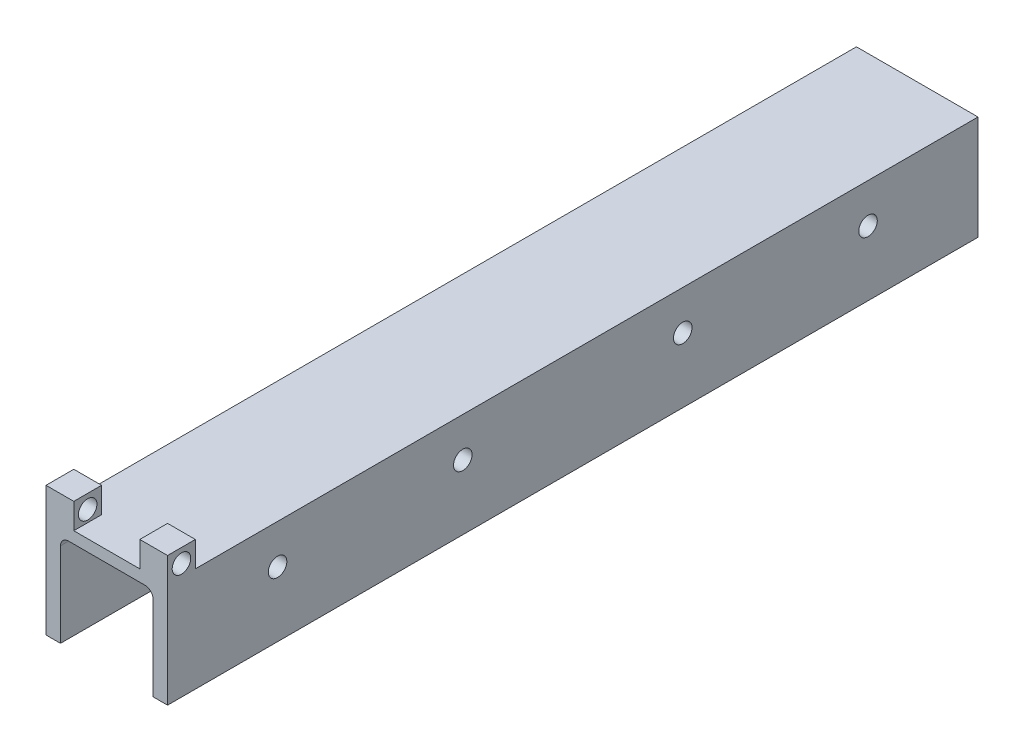
SolidWorks part; units mm, degrees
ref_plane "Front Plane" through (0, 0, 0) normal (0, 0, 1) x (1, 0, 0)
ref_plane "Top Plane" through (0, 0, 0) normal (0, 1, 0) x (1, 0, 0)
ref_plane "Right Plane" through (0, 0, 0) normal (1, 0, 0) x (0, 0, -1)
sketch "Sketch2" plane through (0, 0, 0) normal (0, 0, 1) x (1, 0, 0)
  line L0 (319.8414, 0) -> (-319.8414, 0) construction
  line L2 (0, 0) -> (0, 22.86)
  line L3 (0, 22.86) -> (26.67, 22.86)
  line L4 (26.67, 0) -> (26.67, 22.86)
  line L44 (23.495, 18.542) -> (23.495, 0)
  line L47 (3.175, 0) -> (3.175, 18.542)
  line L48 (4.953, 20.32) -> (21.717, 20.32)
  line L49 (0, 0) -> (3.175, 0)
  line L50 (23.495, 0) -> (26.67, 0)
  arc A0 (23.495, 18.542) -> (21.717, 20.32) centre (21.717, 18.542) ccw
  arc A1 (3.175, 18.542) -> (4.953, 20.32) centre (4.953, 18.542) cw
  point P15 (3.175, 20.32)
  point P16 (3.175, 20.32)
  dimension "D6" = 1.778
  dimension "D1" = 22.86
  dimension "D2" = 26.67
  dimension "D3" = 3.175
  dimension "D4" = 20.32
  dimension "D5" = 3.175
  dimension "D7" = 20.32
extrude "Boss-Extrude2" add sketch "Sketch2" against normal blind 177.8
sketch "Sketch19" plane through (0, 0, 0) normal (1, 0, 0) x (0, 0, -1)
  line L0 (0, 265.0009) -> (0, -265.0009) construction
  line L1 (319.8414, 0) -> (-319.8414, 0) construction
  line L3 (0, 0) -> (88.9, 0) construction
  line L4 (177.8, 0) -> (0, 0) construction
  line L5 (88.9, 0) -> (88.9, 22.86) construction
  line L6 (177.8, 22.86) -> (0, 22.86) construction
  line L7 (177.8, 0) -> (177.8, 22.86) construction
  circle A0 centre (24.13, 14.224) radius 2.032
  circle A1 centre (64.77, 14.224) radius 2.032
  circle A2 centre (113.03, 14.224) radius 2.032
  circle A3 centre (153.67, 14.224) radius 2.032
  dimension "D2" = 4.064
  dimension "D5" = 4.064
  dimension "D9" = 24.13
  dimension "D1" = 24.13
  dimension "D3" = 14.224
  dimension "D4" = 40.64
  dimension "D6" = 14.224
  dimension "D7" = 24.13
  dimension "D8" = 88.9
  dimension "D10" = 40.64
  dimension "D11" = 24.13
extrude "Cut-Extrude3" cut sketch "Sketch19" along normal through all
sketch "Sketch21" plane through (0, 22.86, 0) normal (0, 1, 0) x (1, 0, 0)
  line L0 (13.335, 0) -> (13.335, 177.8) construction
  line L1 (0, 0) -> (26.67, 0) construction
  line L2 (0, 0) -> (6.096, 0)
  line L3 (0, 0) -> (0, 6.096)
  line L4 (0, 6.096) -> (6.096, 6.096)
  line L5 (6.096, 0) -> (6.096, 6.096)
  line L6 (26.67, 177.8) -> (0, 177.8) construction
  line L7 (0, 0) -> (6.096, 0) construction
  line L8 (6.096, 0) -> (6.096, 6.5548) construction
  line L10 (20.574, 0) -> (20.574, 6.5548) construction
  line L11 (26.67, 0) -> (20.574, 0)
  line L12 (26.67, 0) -> (26.67, 6.096)
  line L13 (26.67, 6.096) -> (20.574, 6.096)
  line L14 (20.574, 0) -> (20.574, 6.096)
  dimension "D1" = 6.096
  dimension "D2" = 6.096
  dimension "D3" = 6.096
  dimension "D4" = 14.478
  dimension "D5" = 6.096
  dimension "D6" = 6.096
  dimension "D7" = 6.096
extrude "Boss-Extrude4" add sketch "Sketch21" along normal blind 5.588
sketch "Sketch22" plane through (20.574, 0, 0) normal (-1, 0, 0) x (0, 0, 1)
  line L0 (0, 28.448) -> (-6.096, 28.448) construction
  line L1 (0, -265.0009) -> (0, 265.0009) construction
  circle A0 centre (-3.048, 25.4) radius 2.032
  point P4 (-3.048, 28.448)
  dimension "D1" = 4.064
  dimension "D2" = 3.048
  dimension "D3" = 3.048
extrude "Cut-Extrude4" cut sketch "Sketch22" against normal through all both and the other way through all
